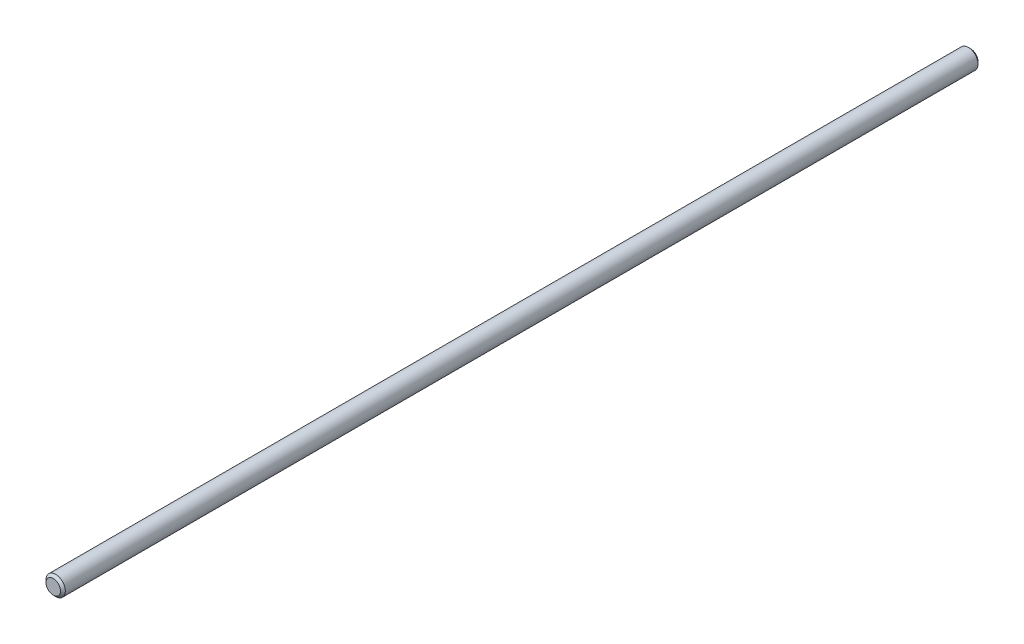
SolidWorks part; units mm, degrees
ref_plane "Piano frontale" through (0, 0, 0) normal (0, 0, 1) x (1, 0, 0)
ref_plane "Piano superiore" through (0, 0, 0) normal (0, 1, 0) x (1, 0, 0)
ref_plane "Piano destro" through (0, 0, 0) normal (1, 0, 0) x (0, 0, -1)
sketch "Schizzo1" plane through (0, 0, 0) normal (0, 0, 1) x (1, 0, 0)
  circle A0 centre (0, 0) radius 4
  dimension "D1" = 8
extrude "Estrusione-Estrusione1" add sketch "Schizzo1" along normal blind 380
chamfer "Smusso1" distance 1 angle 45 2 edges at (4, 0, 380) (4, 0, 0)
